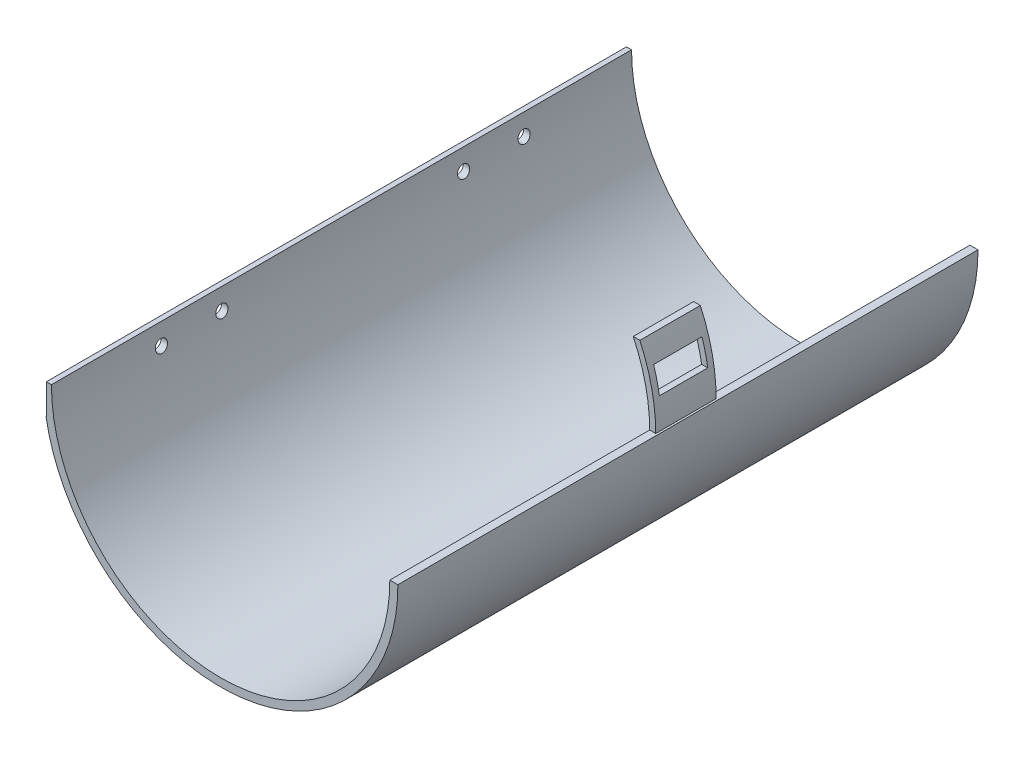
SolidWorks part; units mm, degrees
ref_plane "Front Plane" through (0, 0, 0) normal (0, 0, 1) x (1, 0, 0)
ref_plane "Top Plane" through (0, 0, 0) normal (0, 1, 0) x (1, 0, 0)
ref_plane "Right Plane" through (0, 0, 0) normal (1, 0, 0) x (0, 0, -1)
sketch "Sketch1" plane through (0, 0, 0) normal (0, 0, 1) x (1, 0, 0)
  line L0 (-44, 0) -> (-42, 0)
  line L1 (42, 0) -> (44, 0)
  arc A0 (-44, 0) -> (44, 0) centre (0, 0) ccw
  arc A1 (-42, 0) -> (42, 0) centre (0, 0) ccw
  dimension "D1" = 88
  dimension "D2" = 84
extrude "Boss-Extrude1" add sketch "Sketch1" along normal blind 144
sketch "Sketch2" plane through (0, 0, 0) normal (1, 0, 0) x (0, 0, -1)
  line L0 (-144, 0) -> (-144, -44) construction
  line L1 (0, -44) -> (0, 0) construction
  line L2 (-144, 0) -> (0, 0) construction
  circle A0 centre (-117, -5) radius 1.5
  circle A1 centre (-102, -5) radius 1.5
  circle A2 centre (-42, -5) radius 1.5
  circle A3 centre (-27, -5) radius 1.5
  dimension "D1" = 3
  dimension "D2" = 3
  dimension "D3" = 3
  dimension "D4" = 3
  dimension "D5" = 15
  dimension "D6" = 15
  dimension "D7" = 27
  dimension "D8" = 27
  dimension "D9" = 60
  dimension "D10" = 5
extrude "Cut-Extrude1" cut sketch "Sketch2" against normal up to surface (43.715 mm away) up to face at (0, -22, 72)
ref_plane "Plane1" through (0, 0, 72) normal (0, 0, -1) x (-1, 0, 0)
sketch "Sketch4" plane through (0, 0, 72) normal (0, 0, -1) x (-1, 0, 0)
  line L0 (-39.5677, 18.0735) -> (-37.9124, 18.0735)
  line L1 (-43.5, 0) -> (-42, 0)
  arc A0 (-37.9124, 18.0735) -> (-42, 0) centre (0, 0) ccw
  arc A1 (-39.5677, 18.0735) -> (-43.5, 0) centre (0, 0) ccw
  dimension "D1" = 87
  dimension "D2" = 84
extrude "Boss-Extrude2" add sketch "Sketch4" along normal blind 7.5 and the other way blind 7.5
sketch "Sketch5" plane through (0, 0, 144) normal (0, 0, 1) x (1, 0, 0)
  line L5 (-44, 0) -> (-44, -7.5543)
  line L6 (-44, -7.5543) -> (-42.7628, -7.5543)
  line L7 (-42.7628, -7.5543) -> (-42.7628, 0)
  line L8 (-42, 0) -> (-44, 0) construction
  line L9 (-42.7628, 0) -> (-44, 0)
extrude "Cut-Extrude2" cut sketch "Sketch5" against normal up to surface (144 mm away) up to face at (0, -21.5, 0)
sketch "Sketch6" plane through (-42.7628, 0, 0) normal (-1, 0, 0) x (0, 0, 1)
  line L1 (0, -7.5543) -> (144, -7.5543)
  line L2 (0, -7.5543) -> (0, 0)
  line L3 (0, 0) -> (144, 0)
  line L4 (144, -7.5543) -> (144, 0)
  circle A0 centre (27, -5) radius 1.5
  circle A1 centre (42, -5) radius 1.5
  circle A2 centre (102, -5) radius 1.5
  circle A3 centre (117, -5) radius 1.5
  circle M5 centre (42, -5) radius 1.5
  circle M6 centre (117, -5) radius 1.5
  line M7 (0, 0) -> (0, -7.5543)
  line M8 (0, -7.5543) -> (144, -7.5543)
  line M9 (144, -7.5543) -> (144, 0)
  line M10 (144, 0) -> (0, 0)
  circle M11 centre (102, -5) radius 1.5
  circle M12 centre (27, -5) radius 1.5
extrude "Boss-Extrude3" add sketch "Sketch6" along normal blind 0.5 contours M10 M7 M8 M9 M6 M11 M12 M5 region at (-42.7628, -3.7445, 72)
sketch "Sketch7" plane through (0, 0, 144) normal (0, 0, 1) x (1, 0, 0)
  line L0 (3.2748, -47.7649) -> (4.4051, -46.6346)
  line L2 (2.7338, -44.8136) -> (7.1458, -43.4159)
  line L3 (2.7338, -44.8136) -> (0, -45.5)
  line L4 (-2.7338, -44.8136) -> (-7.1458, -43.4159)
  arc A1 (0, -45.5) -> (3.2748, -47.7649) centre (0, -49) ccw
  arc A2 (-2.7338, -44.8136) -> (4.4051, -46.6346) centre (0, -49) ccw
  arc A3 (-7.1458, -43.4159) -> (7.1458, -43.4159) centre (0, 0) ccw
  dimension "D2" = 7
extrude "Boss-Extrude4" add sketch "Sketch7" against normal blind 77
sketch "Sketch8" plane through (0, 0, 144) normal (0, 0, 1) x (1, 0, 0)
  line L0 (-7.1458, -43.4159) -> (-2.7338, -44.8136)
  line L1 (2.7338, -44.8136) -> (7.1458, -43.4159)
  arc A0 (-7.1458, -43.4159) -> (7.1458, -43.4159) centre (0, 0) ccw
  arc A1 (-2.7338, -44.8136) -> (2.7338, -44.8136) centre (0, -49) ccw
extrude "Cut-Extrude3" cut sketch "Sketch8" against normal blind 67
fillet "Fillet2" radius 1 3 edges at (0, -44, 67) (0, -44, 77) (3.2748, -47.7649, 72)
fillet "Fillet3" radius 0.5 1 edges at (4.4051, -46.6346, 72)
sketch "Sketch9" plane through (0, 0, 0) normal (1, 0, 0) x (0, 0, -1)
  line L0 (-79.5, 18.0735) -> (-79.5, 0) construction
  line L1 (-78, 13.0735) -> (-66, 13.0735)
  line L2 (-78, 13.0735) -> (-78, 7.0735)
  line L3 (-78, 7.0735) -> (-66, 7.0735)
  line L4 (-66, 13.0735) -> (-66, 7.0735)
  line L5 (-79.5, 18.0735) -> (-64.5, 18.0735) construction
  dimension "D1" = 12
  dimension "D2" = 6
  dimension "D3" = 1.5
  dimension "D4" = 5
extrude "Cut-Extrude4" cut sketch "Sketch9" along normal up to surface (41.489 mm away) up to face at (42.0197, 9.1424, 72)
